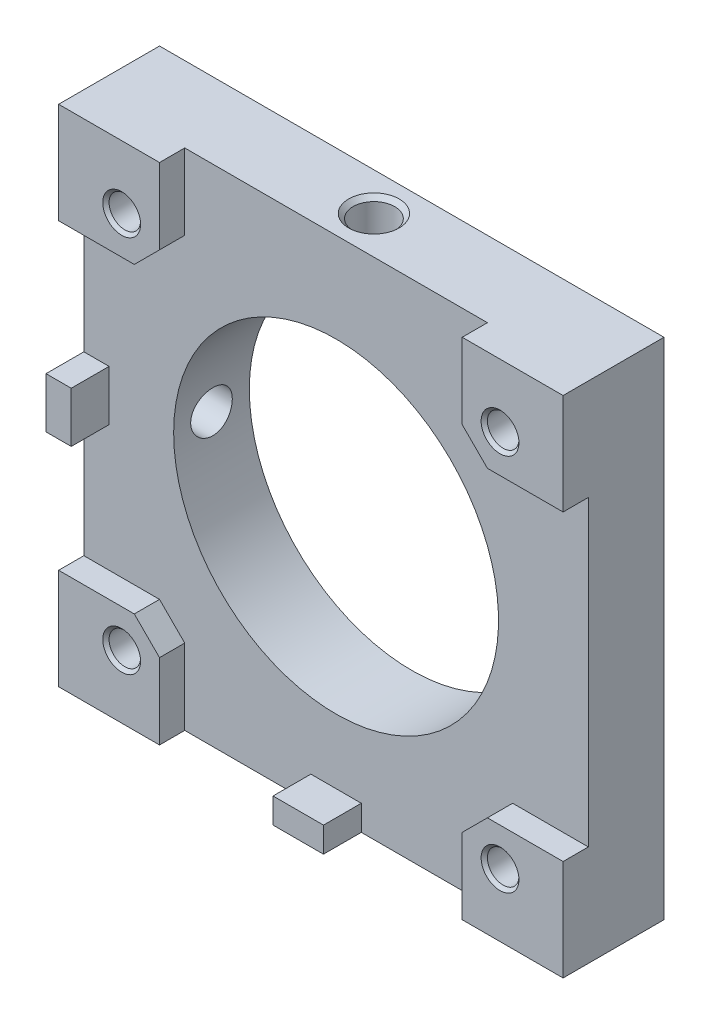
SolidWorks part; units mm, degrees
ref_plane "Front Plane" through (0, 0, 0) normal (0, 0, 1) x (1, 0, 0)
ref_plane "Top Plane" through (0, 0, 0) normal (0, 1, 0) x (1, 0, 0)
ref_plane "Right Plane" through (0, 0, 0) normal (1, 0, 0) x (0, 0, -1)
sketch "Sketch1" plane through (0, 0, 0) normal (0, 0, 1) x (1, 0, 0)
  line L1 (-20, 20) -> (20, 20)
  line L2 (-20, 20) -> (-20, -20)
  line L3 (-20, -20) -> (20, -20)
  line L4 (20, 20) -> (20, -20)
  line L5 (-20, 20) -> (20, -20) construction
  line L6 (-20, -20) -> (20, 20) construction
  point P0 (0, 0)
  dimension "D1" = 40
  dimension "D2" = 40
extrude "Boss-Extrude1" add sketch "Sketch1" along normal mid plane 8
hole_wizard "M3x0.5 Tapped Hole1" positions "Sketch3" profile "Sketch2" tap size "M3x0.5" standard "ANSI Metric" end condition through all
sketch "Sketch3" plane through (0, 0, 4) normal (0, 0, 1) x (1, 0, 0)
  line L0 (15, 15) -> (-15, 15) construction
  line L1 (-15, 15) -> (-15, -15) construction
  line L2 (-15, -15) -> (15, -15) construction
  line L3 (15, -15) -> (15, 15) construction
  line L5 (15, -15) -> (-15, 15) construction
  point P0 (-15, 15)
  point P3 (15, 15)
  point P6 (15, -15)
  point P9 (-15, -15)
  dimension "D1" = 30
sketch "Sketch2" plane through (-15, 15, 4) normal (1, 0, 0) x (0, -1, 0)
  line L0 (0, 0) -> (0, 8)
  line L1 (0, 8) -> (1.25, 8)
  line L2 (1.25, 8) -> (1.25, 0.25)
  line L3 (1.25, 0.25) -> (1.5, 0)
  line L5 (1.5, 0) -> (0, 0)
  line L6 (-1.25, 0.25) -> (-1.5, 0) construction
  line L11 (0, -6.35) -> (0, 107.95) construction
  dimension "Thru Tap Drill Dia." = 2.5
  dimension "Thru Tap Drill Depth" = 8
  dimension "Near C'Sink Dia." = 3
  dimension "Near C'Sink Angle" = 90
cosmetic thread "Hole Thread5" parameters "D2"=3
cosmetic thread "Hole Thread6" parameters "D2"=3
cosmetic thread "Hole Thread7" parameters "D2"=3
cosmetic thread "Hole Thread8" parameters "D2"=3
sketch "Sketch6" plane through (0, 0, 4) normal (0, 0, 1) x (1, 0, 0)
  line L0 (-20, 12) -> (-12, 12)
  line L1 (-20, 20) -> (-20, -20) construction
  line L2 (-12, 12) -> (-12, 20)
  line L3 (20, 20) -> (-20, 20) construction
  line L4 (-12, 20) -> (12, 20)
  line L5 (12, 20) -> (12, 12)
  line L6 (12, 12) -> (20, 12)
  line L7 (20, -20) -> (20, 20) construction
  line L8 (20, 12) -> (20, -12)
  line L9 (20, -12) -> (12, -12)
  line L10 (12, -12) -> (12, -20)
  line L11 (-20, -20) -> (20, -20) construction
  line L12 (12, -20) -> (-12, -20)
  line L13 (-12, -20) -> (-12, -12)
  line L14 (-12, -12) -> (-20, -12)
  line L15 (-20, -12) -> (-20, 12)
  dimension "D1" = 8
  dimension "D2" = 8
  dimension "D3" = 8
  dimension "D4" = 8
  dimension "D5" = 8
  dimension "D6" = 8
  dimension "D7" = 8
  dimension "D8" = 8
extrude "Cut-Extrude1" cut sketch "Sketch6" against normal blind 2
chamfer "Chamfer1" distance 2 angle 45 4 edges at (-12, -12, 3) (12, -12, 3) (12, 12, 3) (-12, 12, 3)
sketch "Sketch7" plane through (0, 0, 2) normal (0, 0, 1) x (1, 0, 0)
  line L0 (-20, 2) -> (-20, -2)
  line L1 (-20, 2) -> (-18, 2)
  line L2 (-20, -2) -> (-18, -2)
  line L3 (-18, 2) -> (-18, -2)
  line L4 (-20, 12) -> (-20, -12) construction
  line L5 (-2, -20) -> (2, -20)
  line L6 (-2, -20) -> (-2, -18)
  line L7 (2, -20) -> (2, -18)
  line L8 (-2, -18) -> (2, -18)
  line L9 (-12, -20) -> (12, -20) construction
  dimension "D1" = 2
  dimension "D2" = 2
  dimension "D3" = 4
  dimension "D4" = 4
  dimension "D5" = 2
  dimension "D6" = 2
extrude "Boss-Extrude2" add sketch "Sketch7" along normal blind 3
sketch "Sketch12" plane through (0, 0, -4) normal (0, 0, -1) x (-1, 0, 0)
  circle A0 centre (0, 0) radius 12.88
  dimension "D1" = 25.76
extrude "Cut-Extrude2" cut sketch "Sketch12" against normal through all
hole_wizard "M4x0.7 Tapped Hole1" positions "Sketch9" profile "Sketch8" tap size "M4x0.7" standard "ANSI Metric" end condition up to next
sketch "Sketch9" plane through (0, 20, 0) normal (0, 1, 0) x (1, 0, 0)
  line L0 (20, 4) -> (-20, 4) construction
  point P0 (0, 1)
  dimension "D1" = 3
cosmetic thread "Hole Thread11" parameters "D2"=4
sketch "Sketch8" plane through (0, 20, -1) normal (1, 0, 0) x (0, 0, 1)
  line L0 (0, 0) -> (0, 7.12)
  line L1 (0, 7.12) -> (1.65, 7.12)
  line L2 (1.65, 7.12) -> (1.65, 0.35)
  line L3 (1.65, 0.35) -> (2, 0)
  line L5 (2, 0) -> (0, 0)
  line L6 (-1.65, 0.35) -> (-2, 0) construction
  line L11 (0, -6.35) -> (0, 107.95) construction
  dimension "Thru Tap Drill Dia." = 3.3
  dimension "Thru Tap Drill Depth" = 7.12
  dimension "Near C'Sink Dia." = 4
  dimension "Near C'Sink Angle" = 90
hole_wizard "M4x0.7 Tapped Hole2" positions "Sketch11" profile "Sketch10" tap size "M4x0.7" standard "ANSI Metric" end condition up to next
sketch "Sketch11" plane through (-20, 0, 0) normal (-1, 0, 0) x (0, 0, 1)
  line L0 (-4, 20) -> (-4, -20) construction
  point P0 (-1, 0)
  dimension "D1" = 3
cosmetic thread "Hole Thread12" parameters "D2"=4
sketch "Sketch10" plane through (-20, 0, -1) normal (0, 1, 0) x (0, 0, 1)
  line L0 (0, 0) -> (0, 7.12)
  line L1 (0, 7.12) -> (1.65, 7.12)
  line L2 (1.65, 7.12) -> (1.65, 0.35)
  line L3 (1.65, 0.35) -> (2, 0)
  line L5 (2, 0) -> (0, 0)
  line L6 (-1.65, 0.35) -> (-2, 0) construction
  line L11 (0, -6.35) -> (0, 107.95) construction
  dimension "Thru Tap Drill Dia." = 3.3
  dimension "Thru Tap Drill Depth" = 7.12
  dimension "Near C'Sink Dia." = 4
  dimension "Near C'Sink Angle" = 90
